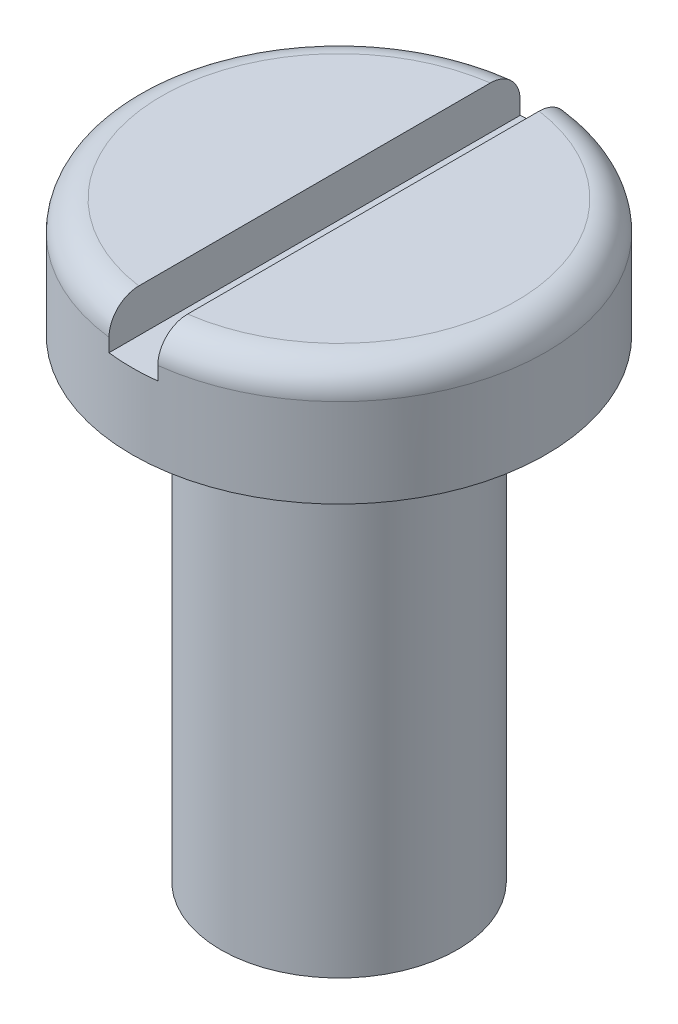
SolidWorks part; units mm, degrees
note: The reader was unsure of these and kept them because the rebuilt part matched: shared geometry of "Sketch1<2>".
ref_plane "Front Plane" through (0, 0, 0) normal (0, 0, 1) x (1, 0, 0)
ref_plane "Top Plane" through (0, 0, 0) normal (0, 1, 0) x (1, 0, 0)
ref_plane "Right Plane" through (0, 0, 0) normal (1, 0, 0) x (0, 0, -1)
sketch "Sketch1" plane through (0, 0, 0) normal (0, 1, 0) x (1, 0, 0)
  circle A0 centre (0, 0) radius 3.5
  circle A1 centre (0, 0) radius 2
  dimension "D1" = 4
  dimension "D2" = 7
extrude "Boss-Extrude1" add sketch "Sketch1" against normal blind 2
extrude "Boss-Extrude2" add sketch "Sketch1<2>" against normal blind 10 contours A1
sketch "Sketch1<2>" plane through (0, 0, 0) normal (0, 1, 0) x (1, 0, 0) same geometry as "Sketch1"
cosmetic thread "Cosmetic Thread1" parameters "D2"=3
sketch "Sketch2" plane through (0, 0, 0) normal (0, 0, 1) x (1, 0, 0)
  line L1 (-0.4125, 0.7268) -> (0.4125, 0.7268)
  line L2 (-0.4125, 0.7268) -> (-0.4125, -0.7268)
  line L3 (-0.4125, -0.7268) -> (0.4125, -0.7268)
  line L4 (0.4125, 0.7268) -> (0.4125, -0.7268)
  line L5 (-0.4125, 0.7268) -> (0.4125, -0.7268) construction
  line L6 (-0.4125, -0.7268) -> (0.4125, 0.7268) construction
  point P0 (0, 0)
extrude "Cut-Extrude1" cut sketch "Sketch2" against normal through all both and the other way through all
fillet "Fillet2" radius 0.5 1 edges at (-3.5, 0, 0)
